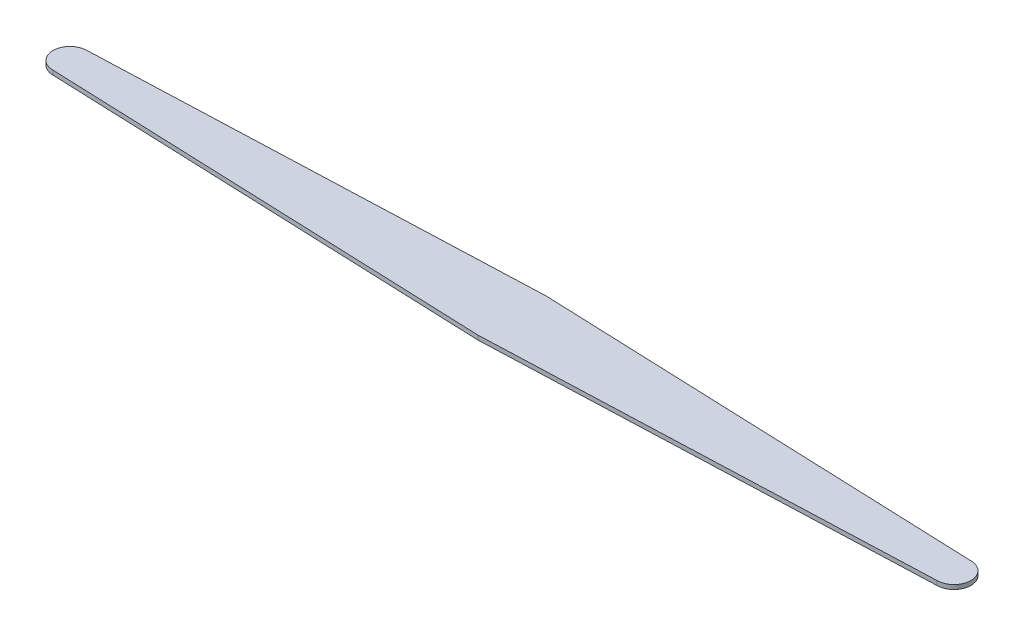
SolidWorks part; units mm, degrees
ref_plane "Front Plane" through (0, 0, 0) normal (0, 0, 1) x (1, 0, 0)
ref_plane "Top Plane" through (0, 0, 0) normal (0, 1, 0) x (1, 0, 0)
ref_plane "Right Plane" through (0, 0, 0) normal (1, 0, 0) x (0, 0, -1)
sketch "Sketch2" plane through (0, 0, 0) normal (0, 1, 0) x (1, 0, 0)
  line L0 (0, 0) -> (0, 25) construction
  line L1 (0, 0) -> (0, -25) construction
  line L2 (0, 0) -> (-325, 0) construction
  line L3 (-325, 12.5) -> (0, 25)
  line L4 (-325, -12.5) -> (0, -25)
  line L5 (325, -12.5) -> (0, -25)
  line L6 (325, 12.5) -> (0, 25)
  arc A0 (-325, 12.5) -> (-325, -12.5) centre (-325, 0) ccw
  arc A1 (325, 12.5) -> (325, -12.5) centre (325, 0) cw
  point P10 (-325, -12.5)
  point P11 (-325, -12.5)
  dimension "D2" = 25
  dimension "D1" = 50
  dimension "Half of Chassis Width" = 325
extrude "Boss-Extrude1" add sketch "Sketch2" along normal blind 3.18
sketch "Sketch3" plane through (0, 3.18, 0) normal (0, 1, 0) x (1, 0, 0)
  line L0 (0, 25) -> (0, -25) construction
  line L1 (-325, 0) -> (0, 0) construction
  line L2 (-232.161, -9.0707) -> (-232.161, 0) construction
  line L3 (-179.5917, 11.0926) -> (-179.5917, 0) construction
  line L4 (-103.1021, -14.0345) -> (-103.1021, 0) construction
  line L5 (-232.161, -9.0707) -> (-232.161, -16.0707) construction
  line L6 (-325, -12.5) -> (0, -25) construction
  line L7 (-179.5917, 11.0926) -> (-179.5917, 18.0926) construction
  line L8 (0, 25) -> (-325, 12.5) construction
  line L9 (-103.1021, -14.0345) -> (-103.1021, -21.0345) construction
  circle A0 centre (0, 0) radius 6.35
  circle A1 centre (-325, 0) radius 3.175
  circle A2 centre (-232.161, -9.0707) radius 1.65
  circle A3 centre (-179.5917, 11.0926) radius 1.65
  circle A4 centre (-103.1021, -14.0345) radius 1.65
  point P16 (0, 0)
  dimension "D1" = 12.7
  dimension "D2" = 6.35
  dimension "D3" = 3.3
  dimension "D4" = 7
  dimension "Hole3" = 232.161
  dimension "Hole2" = 179.5917
  dimension "Hole1" = 103.1021
  dimension "D5" = 7
  dimension "D6" = 7
equation "\"Half of Chassis Width@Sketch2\"= \"Chassis Width@Differential System Assy - Option 1.Assembly\" / 2"
